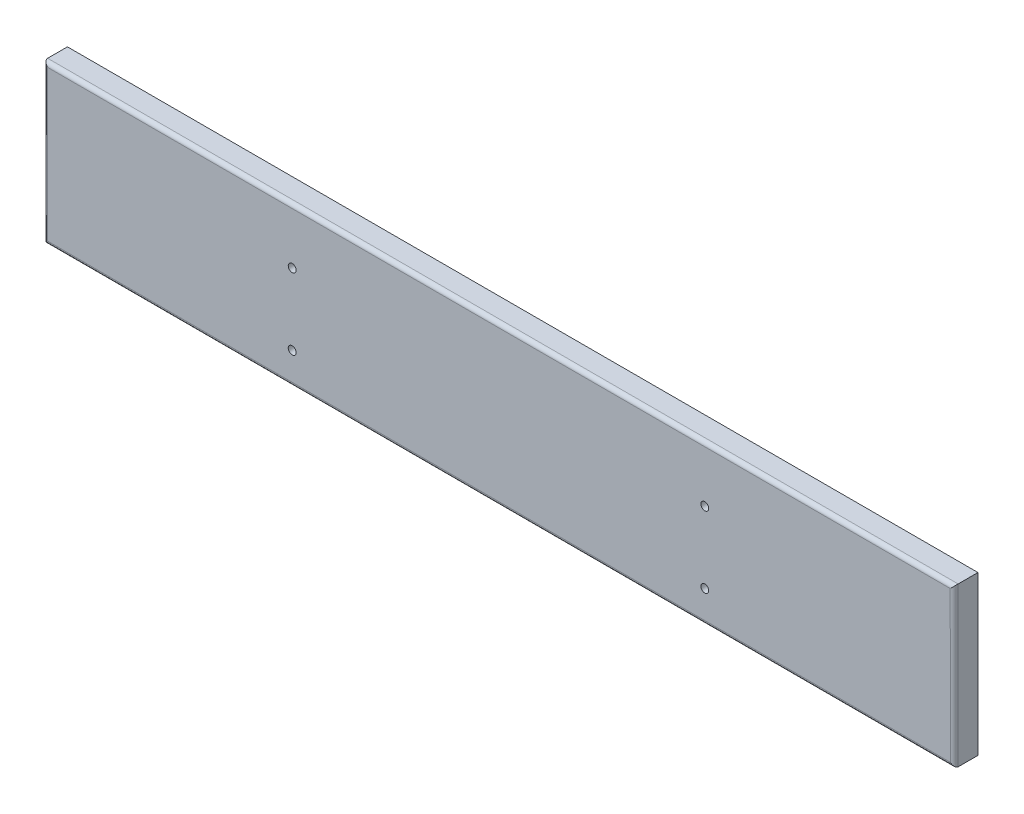
SolidWorks part; units mm, degrees
material "Pine"
ref_plane "Front Plane" through (0, 0, 0) normal (0, 0, 1) x (1, 0, 0)
ref_plane "Top Plane" through (0, 0, 0) normal (0, 1, 0) x (1, 0, 0)
ref_plane "Right Plane" through (0, 0, 0) normal (1, 0, 0) x (0, 0, -1)
sketch "Sketch1" plane through (0, 0, -348.1825) normal (0, 0, 1) x (1, 0, 0)
  line L4 (378.7978, 164.4834) -> (-351.4522, 164.4834)
  line L6 (-351.4522, 37.4834) -> (378.8386, 37.4834)
  line L7 (-351.4522, 164.4834) -> (-351.4522, 37.4834)
  line L8 (378.7978, 164.4834) -> (378.8386, 37.4834)
extrude "Boss-Extrude1" add sketch "Sketch1" along normal blind 19.05 contours L8 L4 L7 L6
hole_wizard "1/4 (0.25) Diameter Hole1" positions "Sketch4" profile "Sketch5" hole size "1/4" standard "ANSI Inch" end condition through all
sketch "Sketch4" plane through (0, 0, -329.1325) normal (0, 0, 1) x (1, 0, 0)
  point P0 (-152.139, 120.0334)
  point P3 (-152.139, 62.8834)
  point P6 (178.7728, 62.8834)
  point P9 (178.7728, 120.0334)
sketch "Sketch5" plane through (-152.139, 120.0334, -329.1325) normal (1, 0, 0) x (0, -1, 0)
  line L0 (0, 0) -> (0, 19.05)
  line L1 (0, 19.05) -> (3.937, 19.05)
  line L2 (3.175, 18.1734) -> (3.175, 0)
  line L5 (3.175, 0) -> (0, 0)
  line L7 (3.937, 19.05) -> (3.175, 18.1734)
  line L8 (-3.937, 19.05) -> (-3.175, 18.1734) construction
  line L11 (0, -6.35) -> (0, 107.95) construction
  dimension "Thru Hole Dia." = 6.35
  dimension "Thru Hole Depth" = 19.05
  dimension "Far C'Sink Dia." = 7.874
  dimension "Far C'Sink Angle" = 82
fillet "Fillet1" radius 3.175 4 edges at (-351.4522, 100.9834, -329.1325) (13.6932, 37.4834, -329.1325) (378.8182, 100.9834, -329.1325) (13.6728, 164.4834, -329.1325)
